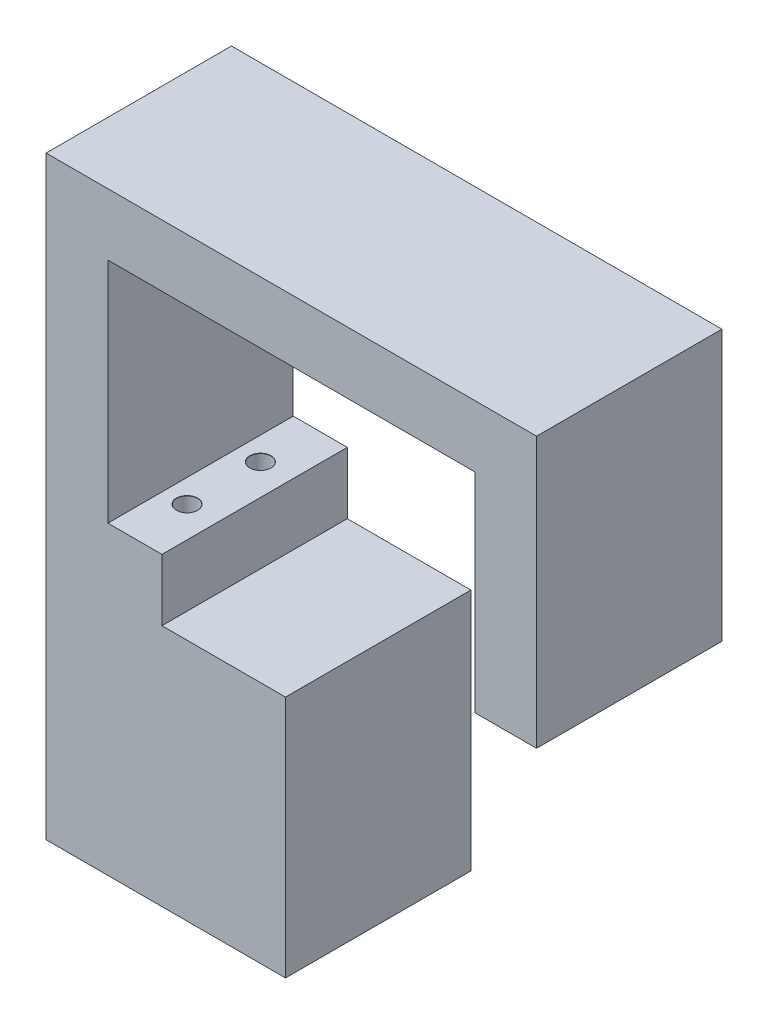
SolidWorks part; units mm, degrees
ref_plane "Front Plane" through (0, 0, 0) normal (0, 0, 1) x (1, 0, 0)
ref_plane "Top Plane" through (0, 0, 0) normal (0, 1, 0) x (1, 0, 0)
ref_plane "Right Plane" through (0, 0, 0) normal (1, 0, 0) x (0, 0, -1)
sketch "Sketch1" plane through (0, 0, 0) normal (0, 0, 1) x (1, 0, 0)
  line L0 (0, 0) -> (-23, 0)
  line L2 (-23, 39.5) -> (-16, 39.5)
  line L3 (-16, 39.5) -> (-16, 31.5)
  line L4 (-16, 31.5) -> (0, 31.5)
  line L5 (0, 31.5) -> (0, 0)
  line L6 (-23, 39.5) -> (-23, 69)
  line L7 (-23, 69) -> (24.5, 69)
  line L8 (24.5, 69) -> (24.5, 42)
  line L9 (24.5, 42) -> (32.5, 42)
  line L10 (32.5, 42) -> (32.5, 77)
  line L11 (32.5, 77) -> (-23.4049, 77)
  line L12 (-23, 0) -> (-31, 0)
  line L13 (-31, 0) -> (-31, 77)
  line L14 (-31, 77) -> (-23.4049, 77)
  point P7 (0, 0)
  point P16 (-23.0031, 39.5)
  point P17 (0, 0)
  point P18 (0, 0)
  dimension "D1" = 16
  dimension "D2" = 31.5
  dimension "D3" = 8
  dimension "D4" = 8
  dimension "D5" = 7
  dimension "D6" = 29.5
  dimension "D7" = 47.5
  dimension "D8" = 27
  dimension "D9" = 8
  dimension "D10" = 8
extrude "Boss-Extrude1" add sketch "Sketch1" along normal mid plane 24
hole_wizard "Ø2.7 (2.7) Diameter Hole1" positions "Sketch2" profile "Sketch3" hole size "Ø2.7" standard "ANSI Metric"
sketch "Sketch2" plane through (0, 39.5, 0) normal (0, 1, 0) x (1, 0, 0)
  line L0 (-16, -12) -> (-16, 12) construction
  line L1 (32.5, -12) -> (-31, -12) construction
  point P0 (-20, 4.75)
  point P2 (-20, -4.75)
  point P7 (0, 0)
  dimension "D1" = 9.5
  dimension "D2" = 4
  dimension "D3" = 7.25
sketch "Sketch3" plane through (-20, 39.5, -4.75) normal (1, 0, 0) x (0, 0, 1)
  line L0 (0, 0) -> (0, 8.8112)
  line L1 (0, 8.8112) -> (1.35, 8)
  line L2 (1.35, 8) -> (1.35, 0.025)
  line L3 (1.35, 0.025) -> (1.375, 0)
  line L5 (1.375, 0) -> (0, 0)
  line L6 (-1.35, 0.025) -> (-1.375, 0) construction
  line L10 (0, 8.8112) -> (-1.35, 8) construction
  line L11 (0, -6.35) -> (0, 107.95) construction
  dimension "Hole Dia." = 2.7
  dimension "Hole Depth" = 8
  dimension "Near C'Sink Dia." = 2.75
  dimension "Near C'Sink Angle" = 90
  dimension "Drill Angle" = 118
hole_wizard "Ø2.7 (2.7) Diameter Hole2" positions "Sketch4" profile "Sketch5" hole size "Ø2.7" standard "ANSI Metric"
sketch "Sketch4" plane through (0, 42, 0) normal (0, -1, 0) x (-1, 0, 0)
  line L1 (-24.5, 12) -> (-32.5, 12) construction
  line L2 (-24.5, -12) -> (-24.5, 12) construction
  point P0 (-28.5, 4.75)
  point P2 (-28.5, -4.75)
  point P7 (0, 0)
  point P10 (0, 0)
  dimension "D1" = 9.5
  dimension "D2" = 4
  dimension "D3" = 7.25
sketch "Sketch5" plane through (28.5, 42, -4.75) normal (1, 0, 0) x (0, 0, -1)
  line L0 (0, 0) -> (0, 8.8112)
  line L1 (0, 8.8112) -> (1.35, 8)
  line L2 (1.35, 8) -> (1.35, 0.025)
  line L3 (1.35, 0.025) -> (1.375, 0)
  line L5 (1.375, 0) -> (0, 0)
  line L6 (-1.35, 0.025) -> (-1.375, 0) construction
  line L10 (0, 8.8112) -> (-1.35, 8) construction
  line L11 (0, -6.35) -> (0, 107.95) construction
  dimension "Hole Dia." = 2.7
  dimension "Hole Depth" = 8
  dimension "Near C'Sink Dia." = 2.75
  dimension "Near C'Sink Angle" = 90
  dimension "Drill Angle" = 118
